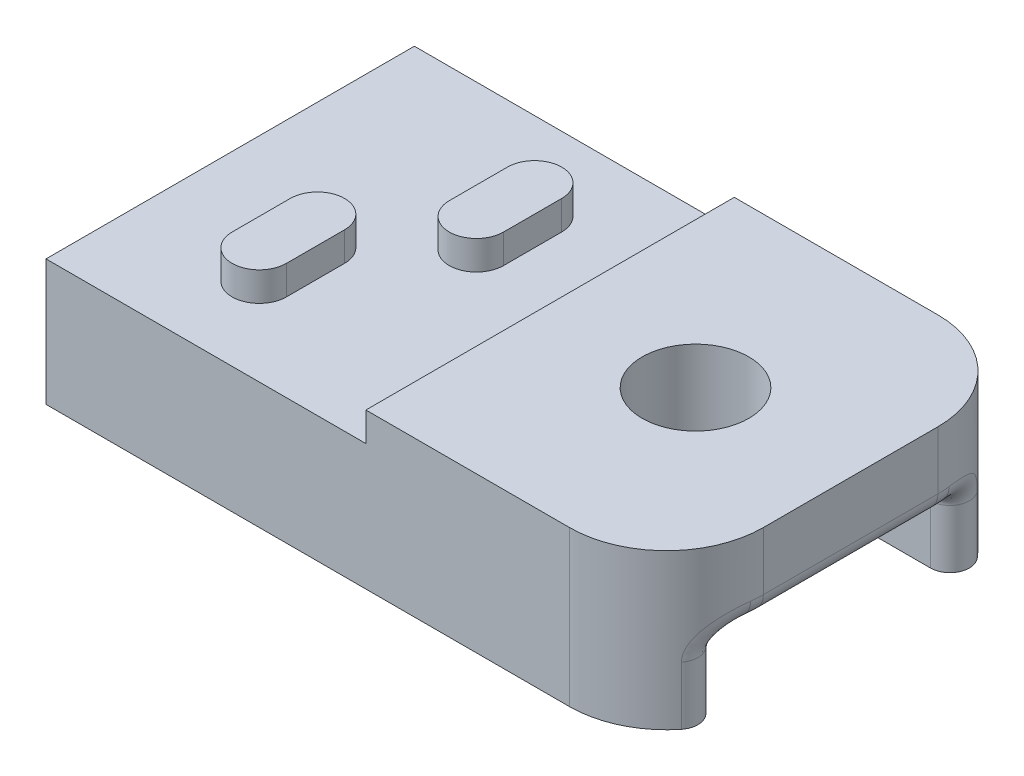
SolidWorks part; units mm, degrees
ref_plane "Front Plane" through (0, 0, 0) normal (0, 0, 1) x (1, 0, 0)
ref_plane "Top Plane" through (0, 0, 0) normal (0, 1, 0) x (1, 0, 0)
ref_plane "Right Plane" through (0, 0, 0) normal (1, 0, 0) x (0, 0, -1)
sketch "Sketch1" plane through (0, 0, 0) normal (0, 1, 0) x (1, 0, 0)
  line L1 (-16, 9.5) -> (16, 9.5)
  line L2 (-16, 9.5) -> (-16, -9.5)
  line L3 (-16, -9.5) -> (16, -9.5)
  line L4 (16, 9.5) -> (16, -9.5)
  line L5 (-16, 9.5) -> (16, -9.5) construction
  line L6 (-16, -9.5) -> (16, 9.5) construction
  point P0 (0, 0)
  dimension "D1" = 19
  dimension "D2" = 32
extrude "Boss-Extrude1" add sketch "Sketch1" along normal blind 8
sketch "Sketch2" plane through (0, 8, 0) normal (0, 1, 0) x (1, 0, 0)
  line L0 (-55, 0) -> (55, 0) construction
  line L1 (16, -9.5) -> (16, 9.5) construction
  circle A0 centre (8, 0) radius 2.75
  dimension "D1" = 5.5
  dimension "D2" = 8
extrude "Cut-Extrude1" cut sketch "Sketch2" against normal up to next
sketch "Sketch4" plane through (0, 8, 0) normal (0, 1, 0) x (1, 0, 0)
  line L1 (-16, 9.5) -> (0.5, 9.5)
  line L2 (-16, 9.5) -> (-16, -9.5)
  line L3 (-16, -9.5) -> (0.5, -9.5)
  line L4 (0.5, 9.5) -> (0.5, -9.5)
  line L5 (-5.3, 5) -> (-5.3, 2) construction
  line L6 (-3.9, 5) -> (-3.9, 2)
  line L7 (-6.7, 5) -> (-6.7, 2)
  line L8 (-9.5, -2) -> (-9.5, -5) construction
  line L9 (-8.1, -2) -> (-8.1, -5)
  line L10 (-10.9, -2) -> (-10.9, -5)
  arc A0 (-3.9, 5) -> (-6.7, 5) centre (-5.3, 5) ccw
  arc A1 (-6.7, 2) -> (-3.9, 2) centre (-5.3, 2) ccw
  arc A2 (-8.1, -2) -> (-10.9, -2) centre (-9.5, -2) ccw
  arc A3 (-10.9, -5) -> (-8.1, -5) centre (-9.5, -5) ccw
  point P9 (-5.3, 3.5)
  point P14 (-9.5, -3.5)
  dimension "D4" = 1.4
  dimension "D6" = 1.4
  dimension "D1" = 19
  dimension "D2" = 4.5
  dimension "D3" = 3
  dimension "D5" = 10.7
  dimension "D7" = 3
  dimension "D8" = 4.5
  dimension "D9" = 6.5
  dimension "D10" = 16.5
extrude "Cut-Extrude2" cut sketch "Sketch4" against normal blind 1.5
fillet "Fillet1" radius 5 2 edges at (16, 4, 9.5) (16, 4, -9.5)
sketch "Sketch6" plane through (0, 0, 0) normal (0, 1, 0) x (1, 0, 0)
  line L0 (-16, 9.5) -> (-16, -9.5) construction
  line L1 (-16, 6) -> (16, 6)
  line L2 (-16, 6) -> (-16, -6)
  line L3 (-16, -6) -> (16, -6)
  line L4 (16, 6) -> (16, -6)
  line L5 (-4.4, 0) -> (4.4, 0) construction
  dimension "D1" = 32
  dimension "D2" = 6
  dimension "D3" = 12
extrude "Cut-Extrude3" cut sketch "Sketch6" along normal blind 4
fillet "Fillet2" radius 1 7 edges at (16, 4, 0) (15.9421, 4, -5.2588) (15.9421, 4, 5.2588) (15.7697, 2, -6) (15.7697, 2, 6) (-0.1152, 4, -6) (-0.1152, 4, 6)
